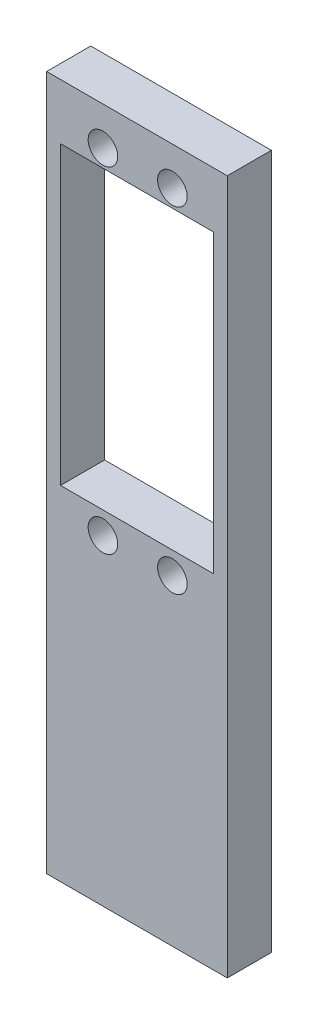
SolidWorks part; units mm, degrees
ref_plane "Front Plane" through (0, 0, 0) normal (0, 0, 1) x (1, 0, 0)
ref_plane "Top Plane" through (0, 0, 0) normal (0, 1, 0) x (1, 0, 0)
ref_plane "Right Plane" through (0, 0, 0) normal (1, 0, 0) x (0, 0, -1)
sketch "Sketch1" plane through (0, 0, 7.303) normal (0, 0, -1) x (-1, 0, 0)
  line L1 (1.3253, -21.2507) -> (27.3253, -21.2507)
  line L2 (1.3253, -21.2507) -> (1.3253, 78.7493)
  line L3 (1.3253, 78.7493) -> (27.3253, 78.7493)
  line L4 (27.3253, -21.2507) -> (27.3253, 78.7493)
  dimension "D1" = 100
  dimension "D2" = 26
extrude "Boss-Extrude1" add sketch "Sketch1" along normal blind 6.35
sketch "Sketch2" plane through (0, 0, 0.953) normal (0, 0, -1) x (-1, 0, 0)
  line L0 (27.3253, -21.2507) -> (27.3253, 78.7493) construction
  line L1 (25.3253, 70.7493) -> (3.3253, 70.7493)
  line L2 (25.3253, 70.7493) -> (25.3253, 28.1493)
  line L3 (25.3253, 28.1493) -> (3.3253, 28.1493)
  line L4 (3.3253, 70.7493) -> (3.3253, 28.1493)
  line L5 (27.3253, 78.7493) -> (1.3253, 78.7493) construction
  dimension "D1" = 22
  dimension "D2" = 42.6
  dimension "D3" = 2
  dimension "D4" = 8
extrude "Cut-Extrude1" cut sketch "Sketch2" against normal through all
hole_wizard "Hole1" positions "Sketch3" profile "Sketch4" legacy end condition through all
sketch "Sketch3" plane through (0, 0, 7.303) normal (0, 0, 1) x (1, 0, 0)
  point P0 (-19.2253, 73.2493)
  point P4 (-9.2253, 73.2493)
  point P7 (-19.2253, 24.9493)
  point P10 (-9.2253, 24.9493)
sketch "Sketch4" plane through (-19.2253, 73.2493, 7.303) normal (1, 0, 0) x (0, -1, 0)
  line L0 (0, 0) -> (0, 6.35)
  line L1 (0, 6.35) -> (2.125, 6.35)
  line L2 (2.125, 6.35) -> (2.125, 0)
  line L3 (2.125, 0) -> (0, 0)
  line L4 (0, 110) -> (0, -10) construction
  dimension "Diameter" = 4.25
  dimension "Depth" = 6.35
